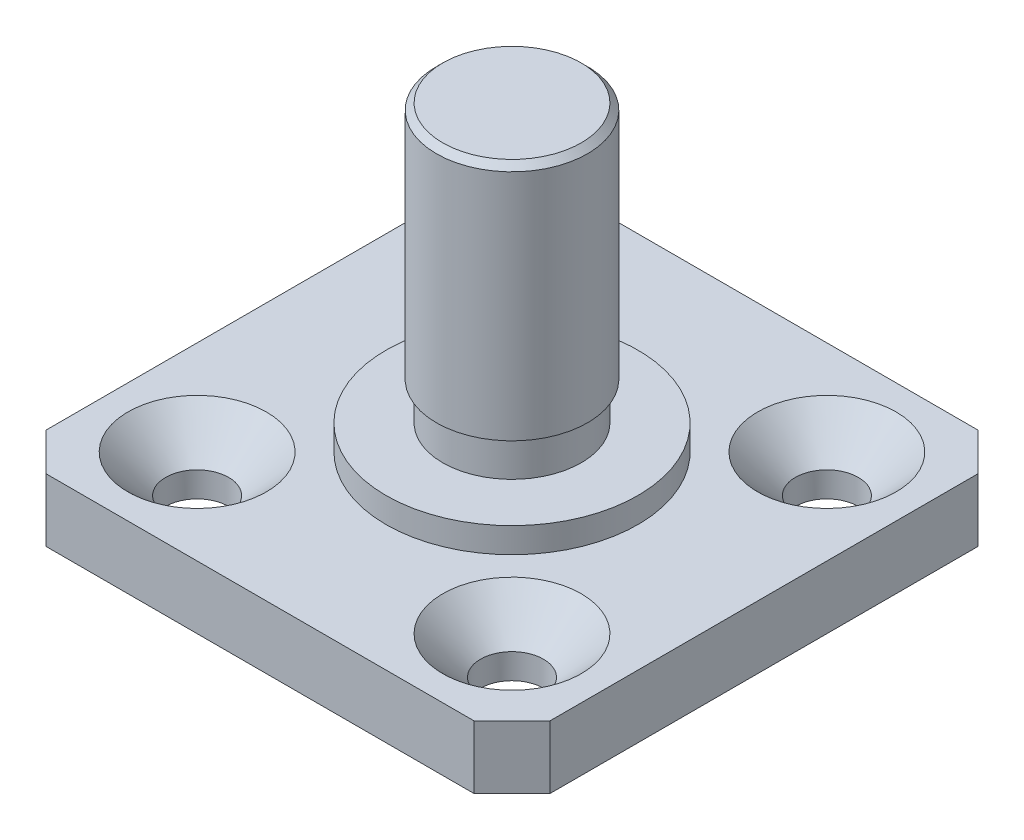
SolidWorks part; units mm, degrees
ref_plane "Спереди" through (0, 0, 0) normal (0, 0, 1) x (1, 0, 0)
ref_plane "Сверху" through (0, 0, 0) normal (0, 1, 0) x (1, 0, 0)
ref_plane "Справа" through (0, 0, 0) normal (1, 0, 0) x (0, 0, -1)
sketch "Эскиз1" plane through (0, 0, 0) normal (0, 1, 0) x (1, 0, 0)
  line L1 (-20, -20) -> (20, -20)
  line L2 (-20, -20) -> (-20, 20)
  line L3 (-20, 20) -> (20, 20)
  line L4 (20, -20) -> (20, 20)
  line L5 (0, 20) -> (0, -20) construction
  line L6 (-20, 0) -> (20, 0) construction
  point P0 (0, 0)
  dimension "D1" = 40
extrude "Бобышка-Вытянуть1" add sketch "Эскиз1" along normal blind 5
chamfer "Фаска1" distance 3 angle 45 4 edges at (-20, 2.5, -20) (20, 2.5, -20) (-20, 2.5, 20) (20, 2.5, 20)
sketch "Эскиз2" plane through (0, 5, 0) normal (0, 1, 0) x (1, 0, 0)
  circle A0 centre (0, 0) radius 10
  dimension "D1" = 20
extrude "Бобышка-Вытянуть2" add sketch "Эскиз2" along normal blind 2
sketch "Эскиз3" plane through (0, 7, 0) normal (0, 1, 0) x (1, 0, 0)
  circle A0 centre (0, 0) radius 6
  dimension "D1" = 12
extrude "Бобышка-Вытянуть3" add sketch "Эскиз3" along normal blind 22
sketch "Эскиз4" plane through (0, 7, 0) normal (0, 1, 0) x (1, 0, 0)
  circle A0 centre (0, 0) radius 6 construction
  circle A1 centre (0, 0) radius 6
  circle A4 centre (0, 0) radius 5.5
  circle A5 centre (0, 0) radius 5.5
  dimension "D1" = 0.5
extrude "Вырез-Вытянуть1" cut sketch "Эскиз4" along normal blind 3
sketch "Эскиз5" plane through (0, 5, 0) normal (0, 1, 0) x (1, 0, 0)
  line L0 (0, 0) -> (0, 8.071) construction
  line L1 (0, 0) -> (4.4681, 0) construction
  circle A0 centre (-12.5, 12.5) radius 2.5
  circle A1 centre (12.5, 12.5) radius 2.5
  circle A2 centre (12.5, -12.5) radius 2.5
  circle A3 centre (-12.5, -12.5) radius 2.5
  point P11 (0, 0)
  point P13 (0, 0)
  point P14 (0, 0)
  point P15 (0, 0)
  dimension "D1" = 5
  dimension "D2" = 25
  dimension "D3" = 25
extrude "Вырез-Вытянуть2" cut sketch "Эскиз5" against normal through all
chamfer "Фаска2" distance 3 angle 45 4 edges at (-12.5, 5, 15) (12.5, 5, 15) (12.5, 5, -10) (-12.5, 5, -10)
chamfer "Фаска3" distance 0.5 angle 45 1 edges at (0, 29, 6)
